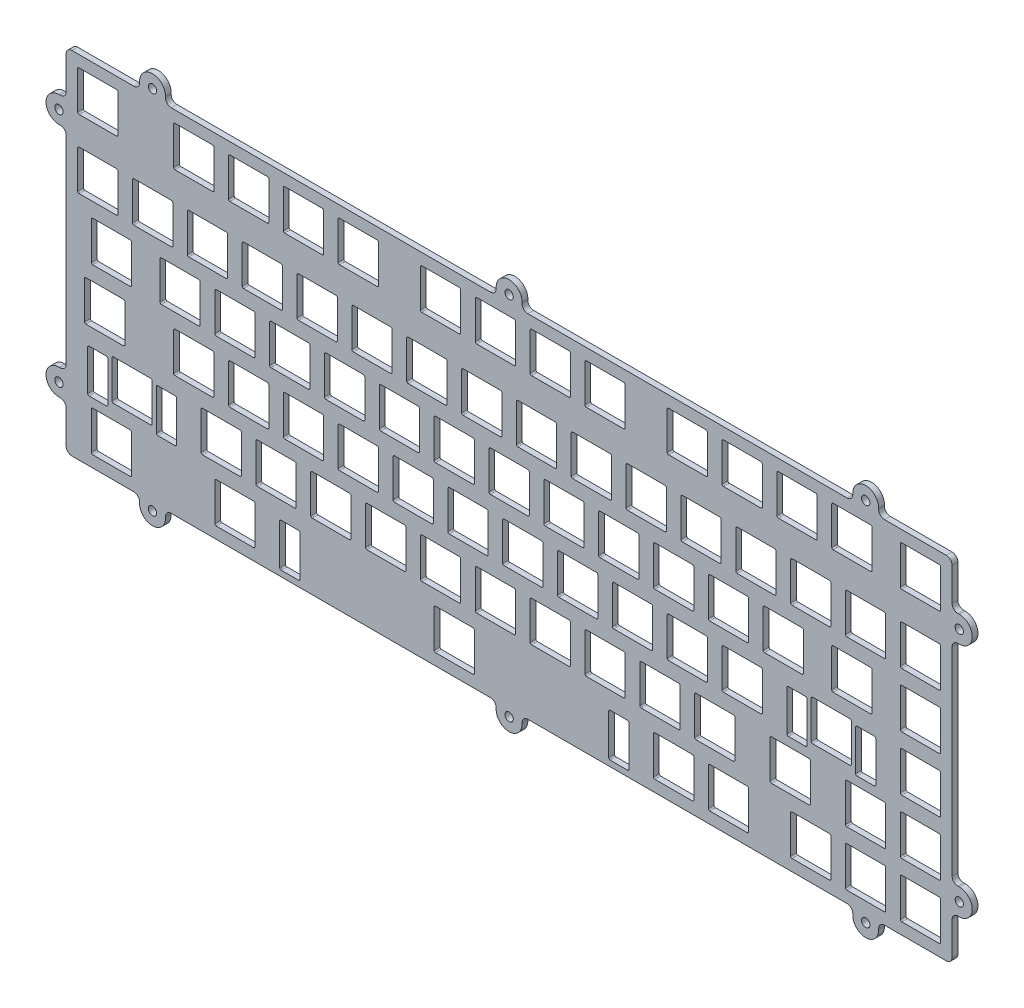
SolidWorks part; units mm, degrees
material "Brass"
ref_plane "Front Plane" through (0, 0, 0) normal (0, 0, 1) x (1, 0, 0)
ref_plane "Top Plane" through (0, 0, 0) normal (0, 1, 0) x (1, 0, 0)
ref_plane "Right Plane" through (0, 0, 0) normal (1, 0, 0) x (0, 0, -1)
sketch "Base_Import_Plate" plane through (0, 0, 0) normal (0, 0, 1) x (1, 0, 0)
  line L0 (12.05, 126.0625) -> (26.05, 126.0625)
  line L1 (12.05, 112.0625) -> (26.05, 112.0625)
  line L2 (12.05, 126.0625) -> (12.05, 112.0625)
  line L3 (26.05, 126.0625) -> (26.05, 112.0625)
  line L4 (45.3875, 126.0625) -> (59.3875, 126.0625)
  line L5 (45.3875, 112.0625) -> (59.3875, 112.0625)
  line L6 (45.3875, 126.0625) -> (45.3875, 112.0625)
  line L7 (59.3875, 126.0625) -> (59.3875, 112.0625)
  line L8 (64.4375, 126.0625) -> (78.4375, 126.0625)
  line L9 (64.4375, 112.0625) -> (78.4375, 112.0625)
  line L10 (64.4375, 126.0625) -> (64.4375, 112.0625)
  line L11 (78.4375, 126.0625) -> (78.4375, 112.0625)
  line L12 (83.4875, 126.0625) -> (97.4875, 126.0625)
  line L13 (83.4875, 112.0625) -> (97.4875, 112.0625)
  line L14 (83.4875, 126.0625) -> (83.4875, 112.0625)
  line L15 (97.4875, 126.0625) -> (97.4875, 112.0625)
  line L16 (102.5375, 126.0625) -> (116.5375, 126.0625)
  line L17 (102.5375, 112.0625) -> (116.5375, 112.0625)
  line L18 (102.5375, 126.0625) -> (102.5375, 112.0625)
  line L19 (116.5375, 126.0625) -> (116.5375, 112.0625)
  line L20 (131.1125, 126.0625) -> (145.1125, 126.0625)
  line L21 (131.1125, 112.0625) -> (145.1125, 112.0625)
  line L22 (131.1125, 126.0625) -> (131.1125, 112.0625)
  line L23 (145.1125, 126.0625) -> (145.1125, 112.0625)
  line L24 (150.1625, 126.0625) -> (164.1625, 126.0625)
  line L25 (150.1625, 112.0625) -> (164.1625, 112.0625)
  line L26 (150.1625, 126.0625) -> (150.1625, 112.0625)
  line L27 (164.1625, 126.0625) -> (164.1625, 112.0625)
  line L28 (169.2125, 126.0625) -> (183.2125, 126.0625)
  line L29 (169.2125, 112.0625) -> (183.2125, 112.0625)
  line L30 (169.2125, 126.0625) -> (169.2125, 112.0625)
  line L31 (183.2125, 126.0625) -> (183.2125, 112.0625)
  line L32 (188.2625, 126.0625) -> (202.2625, 126.0625)
  line L33 (188.2625, 112.0625) -> (202.2625, 112.0625)
  line L34 (188.2625, 126.0625) -> (188.2625, 112.0625)
  line L35 (202.2625, 126.0625) -> (202.2625, 112.0625)
  line L36 (216.8375, 126.0625) -> (230.8375, 126.0625)
  line L37 (216.8375, 112.0625) -> (230.8375, 112.0625)
  line L38 (216.8375, 126.0625) -> (216.8375, 112.0625)
  line L39 (230.8375, 126.0625) -> (230.8375, 112.0625)
  line L40 (235.8875, 126.0625) -> (249.8875, 126.0625)
  line L41 (235.8875, 112.0625) -> (249.8875, 112.0625)
  line L42 (235.8875, 126.0625) -> (235.8875, 112.0625)
  line L43 (249.8875, 126.0625) -> (249.8875, 112.0625)
  line L44 (254.9375, 126.0625) -> (268.9375, 126.0625)
  line L45 (254.9375, 112.0625) -> (268.9375, 112.0625)
  line L46 (254.9375, 126.0625) -> (254.9375, 112.0625)
  line L47 (268.9375, 126.0625) -> (268.9375, 112.0625)
  line L48 (273.9875, 126.0625) -> (287.9875, 126.0625)
  line L49 (273.9875, 112.0625) -> (287.9875, 112.0625)
  line L50 (273.9875, 126.0625) -> (273.9875, 112.0625)
  line L51 (287.9875, 126.0625) -> (287.9875, 112.0625)
  line L52 (297.8, 126.0625) -> (311.8, 126.0625)
  line L53 (297.8, 112.0625) -> (311.8, 112.0625)
  line L54 (297.8, 126.0625) -> (297.8, 112.0625)
  line L55 (311.8, 126.0625) -> (311.8, 112.0625)
  line L56 (12.05, 102.25) -> (26.05, 102.25)
  line L57 (12.05, 88.25) -> (26.05, 88.25)
  line L58 (12.05, 102.25) -> (12.05, 88.25)
  line L59 (26.05, 102.25) -> (26.05, 88.25)
  line L60 (31.1, 102.25) -> (45.1, 102.25)
  line L61 (31.1, 88.25) -> (45.1, 88.25)
  line L62 (31.1, 102.25) -> (31.1, 88.25)
  line L63 (45.1, 102.25) -> (45.1, 88.25)
  line L64 (50.15, 102.25) -> (64.15, 102.25)
  line L65 (50.15, 88.25) -> (64.15, 88.25)
  line L66 (50.15, 102.25) -> (50.15, 88.25)
  line L67 (64.15, 102.25) -> (64.15, 88.25)
  line L68 (69.2, 102.25) -> (83.2, 102.25)
  line L69 (69.2, 88.25) -> (83.2, 88.25)
  line L70 (69.2, 102.25) -> (69.2, 88.25)
  line L71 (83.2, 102.25) -> (83.2, 88.25)
  line L72 (88.25, 102.25) -> (102.25, 102.25)
  line L73 (88.25, 88.25) -> (102.25, 88.25)
  line L74 (88.25, 102.25) -> (88.25, 88.25)
  line L75 (102.25, 102.25) -> (102.25, 88.25)
  line L76 (107.3, 102.25) -> (121.3, 102.25)
  line L77 (107.3, 88.25) -> (121.3, 88.25)
  line L78 (107.3, 102.25) -> (107.3, 88.25)
  line L79 (121.3, 102.25) -> (121.3, 88.25)
  line L80 (126.35, 102.25) -> (140.35, 102.25)
  line L81 (126.35, 88.25) -> (140.35, 88.25)
  line L82 (126.35, 102.25) -> (126.35, 88.25)
  line L83 (140.35, 102.25) -> (140.35, 88.25)
  line L84 (145.4, 102.25) -> (159.4, 102.25)
  line L85 (145.4, 88.25) -> (159.4, 88.25)
  line L86 (145.4, 102.25) -> (145.4, 88.25)
  line L87 (159.4, 102.25) -> (159.4, 88.25)
  line L88 (164.45, 102.25) -> (178.45, 102.25)
  line L89 (164.45, 88.25) -> (178.45, 88.25)
  line L90 (164.45, 102.25) -> (164.45, 88.25)
  line L91 (178.45, 102.25) -> (178.45, 88.25)
  line L92 (183.5, 102.25) -> (197.5, 102.25)
  line L93 (183.5, 88.25) -> (197.5, 88.25)
  line L94 (183.5, 102.25) -> (183.5, 88.25)
  line L95 (197.5, 102.25) -> (197.5, 88.25)
  line L96 (202.55, 102.25) -> (216.55, 102.25)
  line L97 (202.55, 88.25) -> (216.55, 88.25)
  line L98 (202.55, 102.25) -> (202.55, 88.25)
  line L99 (216.55, 102.25) -> (216.55, 88.25)
  line L100 (221.6, 102.25) -> (235.6, 102.25)
  line L101 (221.6, 88.25) -> (235.6, 88.25)
  line L102 (221.6, 102.25) -> (221.6, 88.25)
  line L103 (235.6, 102.25) -> (235.6, 88.25)
  line L104 (240.65, 102.25) -> (254.65, 102.25)
  line L105 (240.65, 88.25) -> (254.65, 88.25)
  line L106 (240.65, 102.25) -> (240.65, 88.25)
  line L107 (254.65, 102.25) -> (254.65, 88.25)
  line L108 (259.7, 102.25) -> (273.7, 102.25)
  line L109 (259.7, 88.25) -> (273.7, 88.25)
  line L110 (259.7, 102.25) -> (259.7, 88.25)
  line L111 (273.7, 102.25) -> (273.7, 88.25)
  line L112 (278.75, 102.25) -> (292.75, 102.25)
  line L113 (278.75, 88.25) -> (292.75, 88.25)
  line L114 (278.75, 102.25) -> (278.75, 88.25)
  line L115 (292.75, 102.25) -> (292.75, 88.25)
  line L116 (297.8, 102.25) -> (311.8, 102.25)
  line L117 (297.8, 88.25) -> (311.8, 88.25)
  line L118 (297.8, 102.25) -> (297.8, 88.25)
  line L119 (311.8, 102.25) -> (311.8, 88.25)
  line L120 (16.8125, 83.2) -> (30.8125, 83.2)
  line L121 (16.8125, 69.2) -> (30.8125, 69.2)
  line L122 (16.8125, 83.2) -> (16.8125, 69.2)
  line L123 (30.8125, 83.2) -> (30.8125, 69.2)
  line L124 (40.625, 83.2) -> (54.625, 83.2)
  line L125 (40.625, 69.2) -> (54.625, 69.2)
  line L126 (40.625, 83.2) -> (40.625, 69.2)
  line L127 (54.625, 83.2) -> (54.625, 69.2)
  line L128 (59.675, 83.2) -> (73.675, 83.2)
  line L129 (59.675, 69.2) -> (73.675, 69.2)
  line L130 (59.675, 83.2) -> (59.675, 69.2)
  line L131 (73.675, 83.2) -> (73.675, 69.2)
  line L132 (78.725, 83.2) -> (92.725, 83.2)
  line L133 (78.725, 69.2) -> (92.725, 69.2)
  line L134 (78.725, 83.2) -> (78.725, 69.2)
  line L135 (92.725, 83.2) -> (92.725, 69.2)
  line L136 (97.775, 83.2) -> (111.775, 83.2)
  line L137 (97.775, 69.2) -> (111.775, 69.2)
  line L138 (97.775, 83.2) -> (97.775, 69.2)
  line L139 (111.775, 83.2) -> (111.775, 69.2)
  line L140 (116.825, 83.2) -> (130.825, 83.2)
  line L141 (116.825, 69.2) -> (130.825, 69.2)
  line L142 (116.825, 83.2) -> (116.825, 69.2)
  line L143 (130.825, 83.2) -> (130.825, 69.2)
  line L144 (135.875, 83.2) -> (149.875, 83.2)
  line L145 (135.875, 69.2) -> (149.875, 69.2)
  line L146 (135.875, 83.2) -> (135.875, 69.2)
  line L147 (149.875, 83.2) -> (149.875, 69.2)
  line L148 (154.925, 83.2) -> (168.925, 83.2)
  line L149 (154.925, 69.2) -> (168.925, 69.2)
  line L150 (154.925, 83.2) -> (154.925, 69.2)
  line L151 (168.925, 83.2) -> (168.925, 69.2)
  line L152 (173.975, 83.2) -> (187.975, 83.2)
  line L153 (173.975, 69.2) -> (187.975, 69.2)
  line L154 (173.975, 83.2) -> (173.975, 69.2)
  line L155 (187.975, 83.2) -> (187.975, 69.2)
  line L156 (193.025, 83.2) -> (207.025, 83.2)
  line L157 (193.025, 69.2) -> (207.025, 69.2)
  line L158 (193.025, 83.2) -> (193.025, 69.2)
  line L159 (207.025, 83.2) -> (207.025, 69.2)
  line L160 (212.075, 83.2) -> (226.075, 83.2)
  line L161 (212.075, 69.2) -> (226.075, 69.2)
  line L162 (212.075, 83.2) -> (212.075, 69.2)
  line L163 (226.075, 83.2) -> (226.075, 69.2)
  line L164 (231.125, 83.2) -> (245.125, 83.2)
  line L165 (231.125, 69.2) -> (245.125, 69.2)
  line L166 (231.125, 83.2) -> (231.125, 69.2)
  line L167 (245.125, 83.2) -> (245.125, 69.2)
  line L168 (250.175, 83.2) -> (264.175, 83.2)
  line L169 (250.175, 69.2) -> (264.175, 69.2)
  line L170 (250.175, 83.2) -> (250.175, 69.2)
  line L171 (264.175, 83.2) -> (264.175, 69.2)
  line L172 (273.9875, 83.2) -> (287.9875, 83.2)
  line L173 (273.9875, 69.2) -> (287.9875, 69.2)
  line L174 (273.9875, 83.2) -> (273.9875, 69.2)
  line L175 (287.9875, 83.2) -> (287.9875, 69.2)
  line L176 (297.8, 83.2) -> (311.8, 83.2)
  line L177 (297.8, 69.2) -> (311.8, 69.2)
  line L178 (297.8, 83.2) -> (297.8, 69.2)
  line L179 (311.8, 83.2) -> (311.8, 69.2)
  line L180 (14.4312, 64.15) -> (28.4312, 64.15)
  line L181 (14.4312, 50.15) -> (28.4312, 50.15)
  line L182 (14.4312, 64.15) -> (14.4312, 50.15)
  line L183 (28.4312, 64.15) -> (28.4312, 50.15)
  line L184 (45.3875, 64.15) -> (59.3875, 64.15)
  line L185 (45.3875, 50.15) -> (59.3875, 50.15)
  line L186 (45.3875, 64.15) -> (45.3875, 50.15)
  line L187 (59.3875, 64.15) -> (59.3875, 50.15)
  line L188 (64.4375, 64.15) -> (78.4375, 64.15)
  line L189 (64.4375, 50.15) -> (78.4375, 50.15)
  line L190 (64.4375, 64.15) -> (64.4375, 50.15)
  line L191 (78.4375, 64.15) -> (78.4375, 50.15)
  line L192 (83.4875, 64.15) -> (97.4875, 64.15)
  line L193 (83.4875, 50.15) -> (97.4875, 50.15)
  line L194 (83.4875, 64.15) -> (83.4875, 50.15)
  line L195 (97.4875, 64.15) -> (97.4875, 50.15)
  line L196 (102.5375, 64.15) -> (116.5375, 64.15)
  line L197 (102.5375, 50.15) -> (116.5375, 50.15)
  line L198 (102.5375, 64.15) -> (102.5375, 50.15)
  line L199 (116.5375, 64.15) -> (116.5375, 50.15)
  line L200 (121.5875, 64.15) -> (135.5875, 64.15)
  line L201 (121.5875, 50.15) -> (135.5875, 50.15)
  line L202 (121.5875, 64.15) -> (121.5875, 50.15)
  line L203 (135.5875, 64.15) -> (135.5875, 50.15)
  line L204 (140.6375, 64.15) -> (154.6375, 64.15)
  line L205 (140.6375, 50.15) -> (154.6375, 50.15)
  line L206 (140.6375, 64.15) -> (140.6375, 50.15)
  line L207 (154.6375, 64.15) -> (154.6375, 50.15)
  line L208 (159.6875, 64.15) -> (173.6875, 64.15)
  line L209 (159.6875, 50.15) -> (173.6875, 50.15)
  line L210 (159.6875, 64.15) -> (159.6875, 50.15)
  line L211 (173.6875, 64.15) -> (173.6875, 50.15)
  line L212 (178.7375, 64.15) -> (192.7375, 64.15)
  line L213 (178.7375, 50.15) -> (192.7375, 50.15)
  line L214 (178.7375, 64.15) -> (178.7375, 50.15)
  line L215 (192.7375, 64.15) -> (192.7375, 50.15)
  line L216 (197.7875, 64.15) -> (211.7875, 64.15)
  line L217 (197.7875, 50.15) -> (211.7875, 50.15)
  line L218 (197.7875, 64.15) -> (197.7875, 50.15)
  line L219 (211.7875, 64.15) -> (211.7875, 50.15)
  line L220 (216.8375, 64.15) -> (230.8375, 64.15)
  line L221 (216.8375, 50.15) -> (230.8375, 50.15)
  line L222 (216.8375, 64.15) -> (216.8375, 50.15)
  line L223 (230.8375, 64.15) -> (230.8375, 50.15)
  line L224 (235.8875, 64.15) -> (249.8875, 64.15)
  line L225 (235.8875, 50.15) -> (249.8875, 50.15)
  line L226 (235.8875, 64.15) -> (235.8875, 50.15)
  line L227 (249.8875, 64.15) -> (249.8875, 50.15)
  line L228 (266.8437, 64.15) -> (280.8437, 64.15)
  line L229 (266.8437, 50.15) -> (280.8437, 50.15)
  line L230 (266.8437, 64.15) -> (266.8437, 50.15)
  line L231 (280.8437, 64.15) -> (280.8437, 50.15)
  line L232 (282.2817, 63.15) -> (289.2817, 63.15)
  line L233 (282.2817, 48.15) -> (289.2817, 48.15)
  line L234 (282.2817, 63.15) -> (282.2817, 48.15)
  line L235 (289.2817, 63.15) -> (289.2817, 48.15)
  line L236 (258.4057, 63.15) -> (265.4057, 63.15)
  line L237 (258.4057, 48.15) -> (265.4057, 48.15)
  line L238 (258.4057, 63.15) -> (258.4057, 48.15)
  line L239 (265.4057, 63.15) -> (265.4057, 48.15)
  line L240 (297.8, 64.15) -> (311.8, 64.15)
  line L241 (297.8, 50.15) -> (311.8, 50.15)
  line L242 (297.8, 64.15) -> (297.8, 50.15)
  line L243 (311.8, 64.15) -> (311.8, 50.15)
  line L244 (23.9562, 45.1) -> (37.9562, 45.1)
  line L245 (23.9562, 31.1) -> (37.9562, 31.1)
  line L246 (23.9562, 45.1) -> (23.9562, 31.1)
  line L247 (37.9562, 45.1) -> (37.9562, 31.1)
  line L248 (39.3942, 44.1) -> (46.3942, 44.1)
  line L249 (39.3942, 29.1) -> (46.3942, 29.1)
  line L250 (39.3942, 44.1) -> (39.3942, 29.1)
  line L251 (46.3942, 44.1) -> (46.3942, 29.1)
  line L252 (15.5182, 44.1) -> (22.5182, 44.1)
  line L253 (15.5182, 29.1) -> (22.5182, 29.1)
  line L254 (15.5182, 44.1) -> (15.5182, 29.1)
  line L255 (22.5182, 44.1) -> (22.5182, 29.1)
  line L256 (54.9125, 45.1) -> (68.9125, 45.1)
  line L257 (54.9125, 31.1) -> (68.9125, 31.1)
  line L258 (54.9125, 45.1) -> (54.9125, 31.1)
  line L259 (68.9125, 45.1) -> (68.9125, 31.1)
  line L260 (73.9625, 45.1) -> (87.9625, 45.1)
  line L261 (73.9625, 31.1) -> (87.9625, 31.1)
  line L262 (73.9625, 45.1) -> (73.9625, 31.1)
  line L263 (87.9625, 45.1) -> (87.9625, 31.1)
  line L264 (93.0125, 45.1) -> (107.0125, 45.1)
  line L265 (93.0125, 31.1) -> (107.0125, 31.1)
  line L266 (93.0125, 45.1) -> (93.0125, 31.1)
  line L267 (107.0125, 45.1) -> (107.0125, 31.1)
  line L268 (112.0625, 45.1) -> (126.0625, 45.1)
  line L269 (112.0625, 31.1) -> (126.0625, 31.1)
  line L270 (112.0625, 45.1) -> (112.0625, 31.1)
  line L271 (126.0625, 45.1) -> (126.0625, 31.1)
  line L272 (131.1125, 45.1) -> (145.1125, 45.1)
  line L273 (131.1125, 31.1) -> (145.1125, 31.1)
  line L274 (131.1125, 45.1) -> (131.1125, 31.1)
  line L275 (145.1125, 45.1) -> (145.1125, 31.1)
  line L276 (150.1625, 45.1) -> (164.1625, 45.1)
  line L277 (150.1625, 31.1) -> (164.1625, 31.1)
  line L278 (150.1625, 45.1) -> (150.1625, 31.1)
  line L279 (164.1625, 45.1) -> (164.1625, 31.1)
  line L280 (169.2125, 45.1) -> (183.2125, 45.1)
  line L281 (169.2125, 31.1) -> (183.2125, 31.1)
  line L282 (169.2125, 45.1) -> (169.2125, 31.1)
  line L283 (183.2125, 45.1) -> (183.2125, 31.1)
  line L284 (188.2625, 45.1) -> (202.2625, 45.1)
  line L285 (188.2625, 31.1) -> (202.2625, 31.1)
  line L286 (188.2625, 45.1) -> (188.2625, 31.1)
  line L287 (202.2625, 45.1) -> (202.2625, 31.1)
  line L288 (207.3125, 45.1) -> (221.3125, 45.1)
  line L289 (207.3125, 31.1) -> (221.3125, 31.1)
  line L290 (207.3125, 45.1) -> (207.3125, 31.1)
  line L291 (221.3125, 45.1) -> (221.3125, 31.1)
  line L292 (226.3625, 45.1) -> (240.3625, 45.1)
  line L293 (226.3625, 31.1) -> (240.3625, 31.1)
  line L294 (226.3625, 45.1) -> (226.3625, 31.1)
  line L295 (240.3625, 45.1) -> (240.3625, 31.1)
  line L296 (252.5562, 45.1) -> (266.5562, 45.1)
  line L297 (252.5562, 31.1) -> (266.5562, 31.1)
  line L298 (252.5562, 45.1) -> (252.5562, 31.1)
  line L299 (266.5562, 45.1) -> (266.5562, 31.1)
  line L300 (278.75, 45.1) -> (292.75, 45.1)
  line L301 (278.75, 31.1) -> (292.75, 31.1)
  line L302 (278.75, 45.1) -> (278.75, 31.1)
  line L303 (292.75, 45.1) -> (292.75, 31.1)
  line L304 (297.8, 45.1) -> (311.8, 45.1)
  line L305 (297.8, 31.1) -> (311.8, 31.1)
  line L306 (297.8, 45.1) -> (297.8, 31.1)
  line L307 (311.8, 45.1) -> (311.8, 31.1)
  line L308 (16.8125, 26.05) -> (30.8125, 26.05)
  line L309 (16.8125, 12.05) -> (30.8125, 12.05)
  line L310 (16.8125, 26.05) -> (16.8125, 12.05)
  line L311 (30.8125, 26.05) -> (30.8125, 12.05)
  line L312 (59.675, 26.05) -> (73.675, 26.05)
  line L313 (59.675, 12.05) -> (73.675, 12.05)
  line L314 (59.675, 26.05) -> (59.675, 12.05)
  line L315 (73.675, 26.05) -> (73.675, 12.05)
  line L316 (135.875, 26.05) -> (149.875, 26.05)
  line L317 (135.875, 12.05) -> (149.875, 12.05)
  line L318 (135.875, 26.05) -> (135.875, 12.05)
  line L319 (149.875, 26.05) -> (149.875, 12.05)
  line L320 (196.525, 25.05) -> (203.525, 25.05)
  line L321 (196.525, 10.05) -> (203.525, 10.05)
  line L322 (196.525, 25.05) -> (196.525, 10.05)
  line L323 (203.525, 25.05) -> (203.525, 10.05)
  line L324 (82.225, 25.05) -> (89.225, 25.05)
  line L325 (82.225, 10.05) -> (89.225, 10.05)
  line L326 (82.225, 25.05) -> (82.225, 10.05)
  line L327 (89.225, 25.05) -> (89.225, 10.05)
  line L328 (212.075, 26.05) -> (226.075, 26.05)
  line L329 (212.075, 12.05) -> (226.075, 12.05)
  line L330 (212.075, 26.05) -> (212.075, 12.05)
  line L331 (226.075, 26.05) -> (226.075, 12.05)
  line L332 (231.125, 26.05) -> (245.125, 26.05)
  line L333 (231.125, 12.05) -> (245.125, 12.05)
  line L334 (231.125, 26.05) -> (231.125, 12.05)
  line L335 (245.125, 26.05) -> (245.125, 12.05)
  line L336 (259.7, 26.05) -> (273.7, 26.05)
  line L337 (259.7, 12.05) -> (273.7, 12.05)
  line L338 (259.7, 26.05) -> (259.7, 12.05)
  line L339 (273.7, 26.05) -> (273.7, 12.05)
  line L340 (278.75, 26.05) -> (292.75, 26.05)
  line L341 (278.75, 12.05) -> (292.75, 12.05)
  line L342 (278.75, 26.05) -> (278.75, 12.05)
  line L343 (292.75, 26.05) -> (292.75, 12.05)
  line L344 (297.8, 26.05) -> (311.8, 26.05)
  line L345 (297.8, 12.05) -> (311.8, 12.05)
  line L346 (297.8, 26.05) -> (297.8, 12.05)
  line L347 (311.8, 26.05) -> (311.8, 12.05)
  circle A0 centre (19.05, 119.0625) radius 2
  circle A1 centre (19.05, 95.25) radius 2
  circle A2 centre (38.1, 95.25) radius 2
  circle A3 centre (52.3875, 119.0625) radius 2
  circle A4 centre (71.4375, 119.0625) radius 2
  circle A5 centre (90.4875, 119.0625) radius 2
  circle A6 centre (109.5375, 119.0625) radius 2
  circle A7 centre (138.1125, 119.0625) radius 2
  circle A8 centre (157.1625, 119.0625) radius 2
  circle A9 centre (176.2125, 119.0625) radius 2
  circle A10 centre (195.2625, 119.0625) radius 2
  circle A11 centre (223.8375, 119.0625) radius 2
  circle A12 centre (242.8875, 119.0625) radius 2
  circle A13 centre (261.9375, 119.0625) radius 2
  circle A14 centre (280.9875, 119.0625) radius 2
  circle A15 centre (304.8, 119.0625) radius 2
  circle A16 centre (57.15, 95.25) radius 2
  circle A17 centre (76.2, 95.25) radius 2
  circle A18 centre (95.25, 95.25) radius 2
  circle A19 centre (114.3, 95.25) radius 2
  circle A20 centre (133.35, 95.25) radius 2
  circle A21 centre (152.4, 95.25) radius 2
  circle A22 centre (171.45, 95.25) radius 2
  circle A23 centre (190.5, 95.25) radius 2
  circle A24 centre (209.55, 95.25) radius 2
  circle A25 centre (228.6, 95.25) radius 2
  circle A26 centre (247.65, 95.25) radius 2
  circle A27 centre (266.7, 95.25) radius 2
  circle A28 centre (285.75, 95.25) radius 2
  circle A29 centre (304.8, 95.25) radius 2
  circle A30 centre (304.8, 76.2) radius 2
  circle A31 centre (304.8, 57.15) radius 2
  circle A32 centre (304.8, 38.1) radius 2
  circle A33 centre (304.8, 19.05) radius 2
  circle A34 centre (285.75, 19.05) radius 2
  circle A35 centre (285.75, 38.1) radius 2
  circle A36 centre (273.8438, 57.15) radius 2
  circle A37 centre (280.9875, 76.2) radius 2
  circle A38 centre (257.175, 76.2) radius 2
  circle A39 centre (238.125, 76.2) radius 2
  circle A40 centre (219.075, 76.2) radius 2
  circle A41 centre (200.025, 76.2) radius 2
  circle A42 centre (180.975, 76.2) radius 2
  circle A43 centre (161.925, 76.2) radius 2
  circle A44 centre (142.875, 76.2) radius 2
  circle A45 centre (123.825, 76.2) radius 2
  circle A46 centre (104.775, 76.2) radius 2
  circle A47 centre (85.725, 76.2) radius 2
  circle A48 centre (66.675, 76.2) radius 2
  circle A49 centre (47.625, 76.2) radius 2
  circle A50 centre (23.8125, 76.2) radius 2
  circle A51 centre (21.4312, 57.15) radius 2
  circle A52 centre (30.9562, 38.1) radius 2
  circle A53 centre (52.3875, 57.15) radius 2
  circle A54 centre (71.4375, 57.15) radius 2
  circle A55 centre (90.4875, 57.15) radius 2
  circle A56 centre (61.9125, 38.1) radius 2
  circle A57 centre (66.675, 19.05) radius 2
  circle A58 centre (23.8125, 19.05) radius 2
  circle A59 centre (142.875, 19.05) radius 2
  circle A60 centre (80.9625, 38.1) radius 2
  circle A61 centre (100.0125, 38.1) radius 2
  circle A62 centre (119.0625, 38.1) radius 2
  circle A63 centre (109.5375, 57.15) radius 2
  circle A64 centre (128.5875, 57.15) radius 2
  circle A65 centre (147.6375, 57.15) radius 2
  circle A66 centre (138.1125, 38.1) radius 2
  circle A67 centre (157.1625, 38.1) radius 2
  circle A68 centre (166.6875, 57.15) radius 2
  circle A69 centre (185.7375, 57.15) radius 2
  circle A70 centre (204.7875, 57.15) radius 2
  circle A71 centre (223.8375, 57.15) radius 2
  circle A72 centre (242.8875, 57.15) radius 2
  circle A73 centre (259.5563, 38.1) radius 2
  circle A74 centre (266.7, 19.05) radius 2
  circle A75 centre (238.125, 19.05) radius 2
  circle A76 centre (219.075, 19.05) radius 2
  circle A77 centre (214.3125, 38.1) radius 2
  circle A78 centre (233.3625, 38.1) radius 2
  circle A79 centre (195.2625, 38.1) radius 2
  circle A80 centre (176.2125, 38.1) radius 2
  dimension "D1" = 19.05
  dimension "D2" = 95.25
sketch "Plate v1" plane through (0, 0, 0) normal (0, 0, 1) x (1, 0, 0)
  line L0 (187.975, 83.2) -> (187.975, 69.2) construction
  line L2 (311.8, 26.05) -> (311.8, 12.05) construction
  line L3 (297.8, 12.05) -> (311.8, 12.05) construction
  line L4 (297.8, 26.05) -> (297.8, 12.05) construction
  line L5 (297.8, 26.05) -> (311.8, 26.05) construction
  line L6 (311.8, 45.1) -> (311.8, 31.1) construction
  line L7 (297.8, 31.1) -> (311.8, 31.1) construction
  line L8 (297.8, 45.1) -> (297.8, 31.1) construction
  line L9 (297.8, 45.1) -> (311.8, 45.1) construction
  line L10 (311.8, 64.15) -> (311.8, 50.15) construction
  line L11 (297.8, 50.15) -> (311.8, 50.15) construction
  line L12 (297.8, 64.15) -> (297.8, 50.15) construction
  line L13 (297.8, 64.15) -> (311.8, 64.15) construction
  line L14 (297.8, 69.2) -> (311.8, 69.2) construction
  line L15 (297.8, 83.2) -> (297.8, 69.2) construction
  line L16 (297.8, 83.2) -> (311.8, 83.2) construction
  line L17 (297.8, 88.25) -> (311.8, 88.25) construction
  line L18 (311.8, 102.25) -> (311.8, 88.25) construction
  line L19 (297.8, 102.25) -> (311.8, 102.25) construction
  line L20 (297.8, 102.25) -> (297.8, 88.25) construction
  line L21 (297.8, 112.0625) -> (311.8, 112.0625) construction
  line L22 (311.8, 126.0625) -> (311.8, 112.0625) construction
  line L23 (297.8, 126.0625) -> (311.8, 126.0625) construction
  line L24 (297.8, 126.0625) -> (297.8, 112.0625) construction
  line L25 (287.9875, 126.0625) -> (287.9875, 112.0625) construction
  line L26 (273.9875, 126.0625) -> (287.9875, 126.0625) construction
  line L27 (273.9875, 126.0625) -> (273.9875, 112.0625) construction
  line L28 (273.9875, 112.0625) -> (287.9875, 112.0625) construction
  line L29 (278.75, 102.25) -> (292.75, 102.25) construction
  line L30 (292.75, 102.25) -> (292.75, 88.25) construction
  line L31 (278.75, 88.25) -> (292.75, 88.25) construction
  line L32 (278.75, 102.25) -> (278.75, 88.25) construction
  line L33 (259.7, 102.25) -> (273.7, 102.25) construction
  line L34 (273.7, 102.25) -> (273.7, 88.25) construction
  line L35 (259.7, 102.25) -> (259.7, 88.25) construction
  line L36 (259.7, 88.25) -> (273.7, 88.25) construction
  line L37 (273.9875, 83.2) -> (287.9875, 83.2) construction
  line L38 (287.9875, 83.2) -> (287.9875, 69.2) construction
  line L39 (273.9875, 69.2) -> (287.9875, 69.2) construction
  line L40 (273.9875, 83.2) -> (273.9875, 69.2) construction
  line L41 (282.2817, 63.15) -> (289.2817, 63.15) construction
  line L42 (289.2817, 63.15) -> (289.2817, 48.15) construction
  line L43 (282.2817, 48.15) -> (289.2817, 48.15) construction
  line L44 (282.2817, 63.15) -> (282.2817, 48.15) construction
  line L45 (280.8437, 64.15) -> (280.8437, 50.15) construction
  line L46 (266.8437, 64.15) -> (280.8437, 64.15) construction
  line L47 (266.8437, 50.15) -> (280.8437, 50.15) construction
  line L48 (266.8437, 64.15) -> (266.8437, 50.15) construction
  line L49 (265.4057, 63.15) -> (265.4057, 48.15) construction
  line L50 (258.4057, 63.15) -> (265.4057, 63.15) construction
  line L51 (258.4057, 63.15) -> (258.4057, 48.15) construction
  line L52 (258.4057, 48.15) -> (265.4057, 48.15) construction
  line L53 (252.5562, 45.1) -> (266.5562, 45.1) construction
  line L54 (266.5562, 45.1) -> (266.5562, 31.1) construction
  line L55 (252.5562, 31.1) -> (266.5562, 31.1) construction
  line L56 (252.5562, 45.1) -> (252.5562, 31.1) construction
  line L57 (278.75, 45.1) -> (292.75, 45.1) construction
  line L58 (292.75, 45.1) -> (292.75, 31.1) construction
  line L59 (278.75, 31.1) -> (292.75, 31.1) construction
  line L60 (278.75, 45.1) -> (278.75, 31.1) construction
  line L61 (292.75, 26.05) -> (292.75, 12.05) construction
  line L62 (278.75, 26.05) -> (292.75, 26.05) construction
  line L63 (278.75, 12.05) -> (292.75, 12.05) construction
  line L64 (278.75, 26.05) -> (278.75, 12.05) construction
  line L65 (273.7, 26.05) -> (273.7, 12.05) construction
  line L66 (259.7, 26.05) -> (273.7, 26.05) construction
  line L67 (259.7, 26.05) -> (259.7, 12.05) construction
  line L68 (259.7, 12.05) -> (273.7, 12.05) construction
  line L69 (245.125, 26.05) -> (245.125, 12.05) construction
  line L70 (231.125, 26.05) -> (245.125, 26.05) construction
  line L71 (231.125, 26.05) -> (231.125, 12.05) construction
  line L72 (231.125, 12.05) -> (245.125, 12.05) construction
  line L73 (226.075, 26.05) -> (226.075, 12.05) construction
  line L74 (212.075, 12.05) -> (226.075, 12.05) construction
  line L75 (212.075, 26.05) -> (226.075, 26.05) construction
  line L76 (212.075, 26.05) -> (212.075, 12.05) construction
  line L77 (207.3125, 31.1) -> (221.3125, 31.1) construction
  line L78 (221.3125, 45.1) -> (221.3125, 31.1) construction
  line L79 (207.3125, 45.1) -> (221.3125, 45.1) construction
  line L80 (207.3125, 45.1) -> (207.3125, 31.1) construction
  line L81 (226.3625, 45.1) -> (226.3625, 31.1) construction
  line L82 (226.3625, 45.1) -> (240.3625, 45.1) construction
  line L83 (240.3625, 45.1) -> (240.3625, 31.1) construction
  line L84 (226.3625, 31.1) -> (240.3625, 31.1) construction
  line L85 (235.8875, 50.15) -> (249.8875, 50.15) construction
  line L86 (249.8875, 64.15) -> (249.8875, 50.15) construction
  line L87 (235.8875, 64.15) -> (249.8875, 64.15) construction
  line L88 (235.8875, 64.15) -> (235.8875, 50.15) construction
  line L89 (250.175, 83.2) -> (250.175, 69.2) construction
  line L90 (250.175, 83.2) -> (264.175, 83.2) construction
  line L91 (264.175, 83.2) -> (264.175, 69.2) construction
  line L92 (250.175, 69.2) -> (264.175, 69.2) construction
  line L93 (254.65, 102.25) -> (254.65, 88.25) construction
  line L94 (240.65, 102.25) -> (254.65, 102.25) construction
  line L95 (240.65, 102.25) -> (240.65, 88.25) construction
  line L96 (240.65, 88.25) -> (254.65, 88.25) construction
  line L97 (231.125, 83.2) -> (245.125, 83.2) construction
  line L98 (245.125, 83.2) -> (245.125, 69.2) construction
  line L99 (231.125, 69.2) -> (245.125, 69.2) construction
  line L100 (231.125, 83.2) -> (231.125, 69.2) construction
  line L101 (235.6, 102.25) -> (235.6, 88.25) construction
  line L102 (221.6, 88.25) -> (235.6, 88.25) construction
  line L103 (221.6, 102.25) -> (235.6, 102.25) construction
  line L104 (221.6, 102.25) -> (221.6, 88.25) construction
  line L105 (254.9375, 112.0625) -> (268.9375, 112.0625) construction
  line L106 (268.9375, 126.0625) -> (268.9375, 112.0625) construction
  line L107 (254.9375, 126.0625) -> (268.9375, 126.0625) construction
  line L108 (254.9375, 126.0625) -> (254.9375, 112.0625) construction
  line L109 (249.8875, 126.0625) -> (249.8875, 112.0625) construction
  line L110 (235.8875, 112.0625) -> (249.8875, 112.0625) construction
  line L111 (235.8875, 126.0625) -> (249.8875, 126.0625) construction
  line L112 (235.8875, 126.0625) -> (235.8875, 112.0625) construction
  line L113 (230.8375, 126.0625) -> (230.8375, 112.0625) construction
  line L114 (216.8375, 112.0625) -> (230.8375, 112.0625) construction
  line L115 (216.8375, 126.0625) -> (230.8375, 126.0625) construction
  line L116 (216.8375, 126.0625) -> (216.8375, 112.0625) construction
  line L117 (188.2625, 112.0625) -> (202.2625, 112.0625) construction
  line L118 (202.2625, 126.0625) -> (202.2625, 112.0625) construction
  line L119 (188.2625, 126.0625) -> (202.2625, 126.0625) construction
  line L120 (188.2625, 126.0625) -> (188.2625, 112.0625) construction
  line L121 (183.2125, 126.0625) -> (183.2125, 112.0625) construction
  line L122 (169.2125, 126.0625) -> (183.2125, 126.0625) construction
  line L123 (150.1625, 126.0625) -> (164.1625, 126.0625) construction
  line L124 (131.1125, 126.0625) -> (145.1125, 126.0625) construction
  line L125 (102.5375, 126.0625) -> (116.5375, 126.0625) construction
  line L126 (83.4875, 126.0625) -> (97.4875, 126.0625) construction
  line L127 (64.4375, 126.0625) -> (78.4375, 126.0625) construction
  line L128 (45.3875, 126.0625) -> (59.3875, 126.0625) construction
  line L129 (12.05, 126.0625) -> (26.05, 126.0625) construction
  line L130 (12.05, 126.0625) -> (12.05, 112.0625) construction
  line L131 (12.05, 112.0625) -> (26.05, 112.0625) construction
  line L132 (26.05, 126.0625) -> (26.05, 112.0625) construction
  line L133 (45.3875, 126.0625) -> (45.3875, 112.0625) construction
  line L134 (45.3875, 112.0625) -> (59.3875, 112.0625) construction
  line L135 (59.3875, 126.0625) -> (59.3875, 112.0625) construction
  line L136 (64.4375, 126.0625) -> (64.4375, 112.0625) construction
  line L137 (64.4375, 112.0625) -> (78.4375, 112.0625) construction
  line L138 (78.4375, 126.0625) -> (78.4375, 112.0625) construction
  line L139 (83.4875, 112.0625) -> (97.4875, 112.0625) construction
  line L140 (97.4875, 126.0625) -> (97.4875, 112.0625) construction
  line L141 (83.4875, 126.0625) -> (83.4875, 112.0625) construction
  line L142 (102.5375, 126.0625) -> (102.5375, 112.0625) construction
  line L143 (116.5375, 126.0625) -> (116.5375, 112.0625) construction
  line L144 (102.5375, 112.0625) -> (116.5375, 112.0625) construction
  line L145 (131.1125, 126.0625) -> (131.1125, 112.0625) construction
  line L146 (131.1125, 112.0625) -> (145.1125, 112.0625) construction
  line L147 (145.1125, 126.0625) -> (145.1125, 112.0625) construction
  line L148 (150.1625, 126.0625) -> (150.1625, 112.0625) construction
  line L149 (164.1625, 126.0625) -> (164.1625, 112.0625) construction
  line L150 (169.2125, 126.0625) -> (169.2125, 112.0625) construction
  line L151 (169.2125, 112.0625) -> (183.2125, 112.0625) construction
  line L152 (150.1625, 112.0625) -> (164.1625, 112.0625) construction
  line L153 (202.55, 102.25) -> (216.55, 102.25) construction
  line L154 (216.55, 102.25) -> (216.55, 88.25) construction
  line L155 (202.55, 88.25) -> (216.55, 88.25) construction
  line L156 (202.55, 102.25) -> (202.55, 88.25) construction
  line L157 (183.5, 102.25) -> (197.5, 102.25) construction
  line L158 (197.5, 102.25) -> (197.5, 88.25) construction
  line L159 (183.5, 88.25) -> (197.5, 88.25) construction
  line L160 (193.025, 83.2) -> (207.025, 83.2) construction
  line L161 (212.075, 83.2) -> (226.075, 83.2) construction
  line L162 (226.075, 83.2) -> (226.075, 69.2) construction
  line L163 (212.075, 69.2) -> (226.075, 69.2) construction
  line L164 (230.8375, 64.15) -> (230.8375, 50.15) construction
  line L165 (216.8375, 64.15) -> (230.8375, 64.15) construction
  line L166 (216.8375, 64.15) -> (216.8375, 50.15) construction
  line L167 (216.8375, 50.15) -> (230.8375, 50.15) construction
  line L168 (202.2625, 45.1) -> (202.2625, 31.1) construction
  line L169 (203.525, 25.05) -> (203.525, 10.05) construction
  line L170 (196.525, 25.05) -> (203.525, 25.05) construction
  line L171 (196.525, 25.05) -> (196.525, 10.05) construction
  line L172 (196.525, 10.05) -> (203.525, 10.05) construction
  line L173 (188.2625, 31.1) -> (202.2625, 31.1) construction
  line L174 (188.2625, 45.1) -> (188.2625, 31.1) construction
  line L175 (188.2625, 45.1) -> (202.2625, 45.1) construction
  line L176 (197.7875, 50.15) -> (211.7875, 50.15) construction
  line L177 (197.7875, 64.15) -> (211.7875, 64.15) construction
  line L178 (211.7875, 64.15) -> (211.7875, 50.15) construction
  line L179 (212.075, 83.2) -> (212.075, 69.2) construction
  line L180 (207.025, 83.2) -> (207.025, 69.2) construction
  line L181 (193.025, 69.2) -> (207.025, 69.2) construction
  line L182 (197.7875, 64.15) -> (197.7875, 50.15) construction
  line L183 (193.025, 83.2) -> (193.025, 69.2) construction
  line L184 (173.975, 83.2) -> (187.975, 83.2) construction
  line L185 (173.975, 69.2) -> (187.975, 69.2) construction
  line L186 (178.7375, 64.15) -> (192.7375, 64.15) construction
  line L187 (192.7375, 64.15) -> (192.7375, 50.15) construction
  line L188 (178.7375, 64.15) -> (178.7375, 50.15) construction
  line L189 (16.8125, 26.05) -> (16.8125, 12.05) construction
  line L190 (16.8125, 12.05) -> (30.8125, 12.05) construction
  line L191 (30.8125, 26.05) -> (30.8125, 12.05) construction
  line L192 (16.8125, 26.05) -> (30.8125, 26.05) construction
  line L193 (22.5182, 44.1) -> (22.5182, 29.1) construction
  line L194 (15.5182, 29.1) -> (22.5182, 29.1) construction
  line L195 (15.5182, 44.1) -> (15.5182, 29.1) construction
  line L196 (15.5182, 44.1) -> (22.5182, 44.1) construction
  line L197 (23.9562, 45.1) -> (23.9562, 31.1) construction
  line L198 (23.9562, 31.1) -> (37.9562, 31.1) construction
  line L199 (23.9562, 45.1) -> (37.9562, 45.1) construction
  line L200 (37.9562, 45.1) -> (37.9562, 31.1) construction
  line L201 (39.3942, 44.1) -> (39.3942, 29.1) construction
  line L202 (39.3942, 29.1) -> (46.3942, 29.1) construction
  line L203 (46.3942, 44.1) -> (46.3942, 29.1) construction
  line L204 (39.3942, 44.1) -> (46.3942, 44.1) construction
  line L205 (45.3875, 64.15) -> (45.3875, 50.15) construction
  line L206 (28.4312, 64.15) -> (28.4312, 50.15) construction
  line L207 (14.4312, 50.15) -> (28.4312, 50.15) construction
  line L208 (14.4312, 64.15) -> (14.4312, 50.15) construction
  line L209 (14.4312, 64.15) -> (28.4312, 64.15) construction
  line L210 (16.8125, 83.2) -> (16.8125, 69.2) construction
  line L211 (16.8125, 69.2) -> (30.8125, 69.2) construction
  line L212 (30.8125, 83.2) -> (30.8125, 69.2) construction
  line L213 (16.8125, 83.2) -> (30.8125, 83.2) construction
  line L214 (12.05, 102.25) -> (12.05, 88.25) construction
  line L215 (12.05, 88.25) -> (26.05, 88.25) construction
  line L216 (26.05, 102.25) -> (26.05, 88.25) construction
  line L217 (12.05, 102.25) -> (26.05, 102.25) construction
  line L218 (31.1, 102.25) -> (31.1, 88.25) construction
  line L219 (31.1, 88.25) -> (45.1, 88.25) construction
  line L220 (45.1, 102.25) -> (45.1, 88.25) construction
  line L221 (31.1, 102.25) -> (45.1, 102.25) construction
  line L222 (50.15, 102.25) -> (50.15, 88.25) construction
  line L223 (50.15, 102.25) -> (64.15, 102.25) construction
  line L224 (64.15, 102.25) -> (64.15, 88.25) construction
  line L225 (50.15, 88.25) -> (64.15, 88.25) construction
  line L226 (40.625, 83.2) -> (40.625, 69.2) construction
  line L227 (54.625, 83.2) -> (54.625, 69.2) construction
  line L228 (40.625, 83.2) -> (54.625, 83.2) construction
  line L229 (40.625, 69.2) -> (54.625, 69.2) construction
  line L230 (45.3875, 64.15) -> (59.3875, 64.15) construction
  line L231 (45.3875, 50.15) -> (59.3875, 50.15) construction
  line L232 (59.3875, 64.15) -> (59.3875, 50.15) construction
  line L233 (54.9125, 45.1) -> (54.9125, 31.1) construction
  line L234 (54.9125, 45.1) -> (68.9125, 45.1) construction
  line L235 (68.9125, 45.1) -> (68.9125, 31.1) construction
  line L236 (54.9125, 31.1) -> (68.9125, 31.1) construction
  line L237 (59.675, 12.05) -> (73.675, 12.05) construction
  line L238 (59.675, 26.05) -> (59.675, 12.05) construction
  line L239 (59.675, 26.05) -> (73.675, 26.05) construction
  line L240 (73.675, 26.05) -> (73.675, 12.05) construction
  line L241 (82.225, 25.05) -> (82.225, 10.05) construction
  line L242 (82.225, 10.05) -> (89.225, 10.05) construction
  line L243 (89.225, 25.05) -> (89.225, 10.05) construction
  line L244 (82.225, 25.05) -> (89.225, 25.05) construction
  line L245 (73.9625, 31.1) -> (87.9625, 31.1) construction
  line L246 (73.9625, 45.1) -> (73.9625, 31.1) construction
  line L247 (73.9625, 45.1) -> (87.9625, 45.1) construction
  line L248 (64.4375, 64.15) -> (64.4375, 50.15) construction
  line L249 (64.4375, 50.15) -> (78.4375, 50.15) construction
  line L250 (78.4375, 64.15) -> (78.4375, 50.15) construction
  line L251 (64.4375, 64.15) -> (78.4375, 64.15) construction
  line L252 (59.675, 83.2) -> (59.675, 69.2) construction
  line L253 (59.675, 69.2) -> (73.675, 69.2) construction
  line L254 (73.675, 83.2) -> (73.675, 69.2) construction
  line L255 (59.675, 83.2) -> (73.675, 83.2) construction
  line L256 (78.725, 83.2) -> (78.725, 69.2) construction
  line L257 (78.725, 69.2) -> (92.725, 69.2) construction
  line L258 (83.4875, 64.15) -> (83.4875, 50.15) construction
  line L259 (87.9625, 45.1) -> (87.9625, 31.1) construction
  line L260 (93.0125, 45.1) -> (93.0125, 31.1) construction
  line L261 (83.4875, 50.15) -> (97.4875, 50.15) construction
  line L262 (97.775, 83.2) -> (97.775, 69.2) construction
  line L263 (92.725, 83.2) -> (92.725, 69.2) construction
  line L264 (97.4875, 64.15) -> (97.4875, 50.15) construction
  line L265 (83.4875, 64.15) -> (97.4875, 64.15) construction
  line L266 (102.5375, 64.15) -> (102.5375, 50.15) construction
  line L267 (97.775, 69.2) -> (111.775, 69.2) construction
  line L268 (111.775, 83.2) -> (111.775, 69.2) construction
  line L269 (116.825, 83.2) -> (116.825, 69.2) construction
  line L270 (116.825, 83.2) -> (130.825, 83.2) construction
  line L271 (97.775, 83.2) -> (111.775, 83.2) construction
  line L272 (78.725, 83.2) -> (92.725, 83.2) construction
  line L273 (69.2, 102.25) -> (69.2, 88.25) construction
  line L274 (69.2, 88.25) -> (83.2, 88.25) construction
  line L275 (83.2, 102.25) -> (83.2, 88.25) construction
  line L276 (69.2, 102.25) -> (83.2, 102.25) construction
  line L277 (88.25, 102.25) -> (88.25, 88.25) construction
  line L278 (88.25, 88.25) -> (102.25, 88.25) construction
  line L279 (88.25, 102.25) -> (102.25, 102.25) construction
  line L280 (102.25, 102.25) -> (102.25, 88.25) construction
  line L281 (107.3, 102.25) -> (107.3, 88.25) construction
  line L282 (107.3, 88.25) -> (121.3, 88.25) construction
  line L283 (107.3, 102.25) -> (121.3, 102.25) construction
  line L284 (121.3, 102.25) -> (121.3, 88.25) construction
  line L285 (126.35, 102.25) -> (126.35, 88.25) construction
  line L286 (126.35, 102.25) -> (140.35, 102.25) construction
  line L287 (140.35, 102.25) -> (140.35, 88.25) construction
  line L288 (126.35, 88.25) -> (140.35, 88.25) construction
  line L289 (130.825, 83.2) -> (130.825, 69.2) construction
  line L290 (116.825, 69.2) -> (130.825, 69.2) construction
  line L291 (112.0625, 45.1) -> (112.0625, 31.1) construction
  line L292 (102.5375, 64.15) -> (116.5375, 64.15) construction
  line L293 (116.5375, 64.15) -> (116.5375, 50.15) construction
  line L294 (102.5375, 50.15) -> (116.5375, 50.15) construction
  line L295 (93.0125, 31.1) -> (107.0125, 31.1) construction
  line L296 (93.0125, 45.1) -> (107.0125, 45.1) construction
  line L297 (107.0125, 45.1) -> (107.0125, 31.1) construction
  line L298 (112.0625, 31.1) -> (126.0625, 31.1) construction
  line L299 (112.0625, 45.1) -> (126.0625, 45.1) construction
  line L300 (126.0625, 45.1) -> (126.0625, 31.1) construction
  line L301 (121.5875, 64.15) -> (121.5875, 50.15) construction
  line L302 (121.5875, 50.15) -> (135.5875, 50.15) construction
  line L303 (135.5875, 64.15) -> (135.5875, 50.15) construction
  line L304 (135.875, 83.2) -> (135.875, 69.2) construction
  line L305 (121.5875, 64.15) -> (135.5875, 64.15) construction
  line L306 (140.6375, 64.15) -> (140.6375, 50.15) construction
  line L307 (140.6375, 64.15) -> (154.6375, 64.15) construction
  line L308 (135.875, 69.2) -> (149.875, 69.2) construction
  line L309 (149.875, 83.2) -> (149.875, 69.2) construction
  line L310 (154.925, 83.2) -> (154.925, 69.2) construction
  line L311 (135.875, 83.2) -> (149.875, 83.2) construction
  line L312 (145.4, 88.25) -> (159.4, 88.25) construction
  line L313 (145.4, 102.25) -> (145.4, 88.25) construction
  line L314 (145.4, 102.25) -> (159.4, 102.25) construction
  line L315 (159.4, 102.25) -> (159.4, 88.25) construction
  line L316 (183.2125, 45.1) -> (183.2125, 31.1) construction
  line L317 (169.2125, 45.1) -> (169.2125, 31.1) construction
  line L318 (154.6375, 64.15) -> (154.6375, 50.15) construction
  line L319 (140.6375, 50.15) -> (154.6375, 50.15) construction
  line L320 (131.1125, 45.1) -> (145.1125, 45.1) construction
  line L321 (131.1125, 45.1) -> (131.1125, 31.1) construction
  line L322 (135.875, 26.05) -> (135.875, 12.05) construction
  line L323 (135.875, 12.05) -> (149.875, 12.05) construction
  line L324 (149.875, 26.05) -> (149.875, 12.05) construction
  line L325 (135.875, 26.05) -> (149.875, 26.05) construction
  line L326 (131.1125, 31.1) -> (145.1125, 31.1) construction
  line L327 (145.1125, 45.1) -> (145.1125, 31.1) construction
  line L328 (150.1625, 45.1) -> (150.1625, 31.1) construction
  line L329 (150.1625, 45.1) -> (164.1625, 45.1) construction
  line L330 (164.1625, 45.1) -> (164.1625, 31.1) construction
  line L331 (150.1625, 31.1) -> (164.1625, 31.1) construction
  line L332 (169.2125, 31.1) -> (183.2125, 31.1) construction
  line L333 (169.2125, 45.1) -> (183.2125, 45.1) construction
  line L334 (159.6875, 64.15) -> (159.6875, 50.15) construction
  line L335 (173.6875, 64.15) -> (173.6875, 50.15) construction
  line L336 (159.6875, 50.15) -> (173.6875, 50.15) construction
  line L337 (159.6875, 64.15) -> (173.6875, 64.15) construction
  line L338 (154.925, 69.2) -> (168.925, 69.2) construction
  line L339 (168.925, 83.2) -> (168.925, 69.2) construction
  line L340 (154.925, 83.2) -> (168.925, 83.2) construction
  line L341 (164.45, 88.25) -> (178.45, 88.25) construction
  line L342 (164.45, 102.25) -> (164.45, 88.25) construction
  line L343 (164.45, 102.25) -> (178.45, 102.25) construction
  line L344 (183.5, 102.25) -> (183.5, 88.25) construction
  line L345 (178.45, 102.25) -> (178.45, 88.25) construction
  line L346 (173.975, 83.2) -> (173.975, 69.2) construction
  line L347 (16.8125, 26.05) -> (16.8125, 12.05)
  line L348 (16.8125, 12.05) -> (30.8125, 12.05)
  line L349 (30.8125, 26.05) -> (30.8125, 12.05)
  line L350 (16.8125, 26.05) -> (30.8125, 26.05)
  line L351 (22.5182, 44.1) -> (22.5182, 29.1)
  line L352 (15.5182, 29.1) -> (22.5182, 29.1)
  line L353 (15.5182, 44.1) -> (15.5182, 29.1)
  line L354 (15.5182, 44.1) -> (22.5182, 44.1)
  line L355 (23.9562, 45.1) -> (23.9562, 31.1)
  line L356 (23.9562, 31.1) -> (37.9562, 31.1)
  line L357 (23.9562, 45.1) -> (37.9562, 45.1)
  line L358 (37.9562, 45.1) -> (37.9562, 31.1)
  line L359 (39.3942, 44.1) -> (39.3942, 29.1)
  line L360 (39.3942, 29.1) -> (46.3942, 29.1)
  line L361 (46.3942, 44.1) -> (46.3942, 29.1)
  line L362 (39.3942, 44.1) -> (46.3942, 44.1)
  line L363 (45.3875, 64.15) -> (45.3875, 50.15)
  line L364 (28.4312, 64.15) -> (28.4312, 50.15)
  line L365 (14.4312, 50.15) -> (28.4312, 50.15)
  line L366 (14.4312, 64.15) -> (14.4312, 50.15)
  line L367 (14.4312, 64.15) -> (28.4312, 64.15)
  line L368 (16.8125, 83.2) -> (16.8125, 69.2)
  line L369 (16.8125, 69.2) -> (30.8125, 69.2)
  line L370 (30.8125, 83.2) -> (30.8125, 69.2)
  line L371 (16.8125, 83.2) -> (30.8125, 83.2)
  line L372 (12.05, 102.25) -> (12.05, 88.25)
  line L373 (12.05, 88.25) -> (26.05, 88.25)
  line L374 (26.05, 102.25) -> (26.05, 88.25)
  line L375 (12.05, 102.25) -> (26.05, 102.25)
  line L376 (31.1, 102.25) -> (31.1, 88.25)
  line L377 (31.1, 88.25) -> (45.1, 88.25)
  line L378 (45.1, 102.25) -> (45.1, 88.25)
  line L379 (31.1, 102.25) -> (45.1, 102.25)
  line L380 (50.15, 102.25) -> (50.15, 88.25)
  line L381 (50.15, 102.25) -> (64.15, 102.25)
  line L382 (64.15, 102.25) -> (64.15, 88.25)
  line L383 (50.15, 88.25) -> (64.15, 88.25)
  line L384 (40.625, 83.2) -> (40.625, 69.2)
  line L385 (54.625, 83.2) -> (54.625, 69.2)
  line L386 (40.625, 83.2) -> (54.625, 83.2)
  line L387 (40.625, 69.2) -> (54.625, 69.2)
  line L388 (45.3875, 64.15) -> (59.3875, 64.15)
  line L389 (45.3875, 50.15) -> (59.3875, 50.15)
  line L390 (59.3875, 64.15) -> (59.3875, 50.15)
  line L391 (54.9125, 45.1) -> (54.9125, 31.1)
  line L392 (54.9125, 45.1) -> (68.9125, 45.1)
  line L393 (68.9125, 45.1) -> (68.9125, 31.1)
  line L394 (54.9125, 31.1) -> (68.9125, 31.1)
  line L395 (59.675, 12.05) -> (73.675, 12.05)
  line L396 (59.675, 26.05) -> (59.675, 12.05)
  line L397 (59.675, 26.05) -> (73.675, 26.05)
  line L398 (73.675, 26.05) -> (73.675, 12.05)
  line L399 (82.225, 25.05) -> (82.225, 10.05)
  line L400 (82.225, 10.05) -> (89.225, 10.05)
  line L401 (89.225, 25.05) -> (89.225, 10.05)
  line L402 (82.225, 25.05) -> (89.225, 25.05)
  line L403 (73.9625, 31.1) -> (87.9625, 31.1)
  line L404 (73.9625, 45.1) -> (73.9625, 31.1)
  line L405 (73.9625, 45.1) -> (87.9625, 45.1)
  line L406 (64.4375, 64.15) -> (64.4375, 50.15)
  line L407 (64.4375, 50.15) -> (78.4375, 50.15)
  line L408 (78.4375, 64.15) -> (78.4375, 50.15)
  line L409 (64.4375, 64.15) -> (78.4375, 64.15)
  line L410 (59.675, 83.2) -> (59.675, 69.2)
  line L411 (59.675, 69.2) -> (73.675, 69.2)
  line L412 (73.675, 83.2) -> (73.675, 69.2)
  line L413 (59.675, 83.2) -> (73.675, 83.2)
  line L414 (78.725, 83.2) -> (78.725, 69.2)
  line L415 (78.725, 69.2) -> (92.725, 69.2)
  line L416 (83.4875, 64.15) -> (83.4875, 50.15)
  line L417 (87.9625, 45.1) -> (87.9625, 31.1)
  line L418 (93.0125, 45.1) -> (93.0125, 31.1)
  line L419 (83.4875, 50.15) -> (97.4875, 50.15)
  line L420 (97.775, 83.2) -> (97.775, 69.2)
  line L421 (92.725, 83.2) -> (92.725, 69.2)
  line L422 (97.4875, 64.15) -> (97.4875, 50.15)
  line L423 (83.4875, 64.15) -> (97.4875, 64.15)
  line L424 (102.5375, 64.15) -> (102.5375, 50.15)
  line L425 (97.775, 69.2) -> (111.775, 69.2)
  line L426 (111.775, 83.2) -> (111.775, 69.2)
  line L427 (116.825, 83.2) -> (116.825, 69.2)
  line L428 (116.825, 83.2) -> (130.825, 83.2)
  line L429 (97.775, 83.2) -> (111.775, 83.2)
  line L430 (78.725, 83.2) -> (92.725, 83.2)
  line L431 (69.2, 102.25) -> (69.2, 88.25)
  line L432 (69.2, 88.25) -> (83.2, 88.25)
  line L433 (83.2, 102.25) -> (83.2, 88.25)
  line L434 (69.2, 102.25) -> (83.2, 102.25)
  line L435 (88.25, 102.25) -> (88.25, 88.25)
  line L436 (88.25, 88.25) -> (102.25, 88.25)
  line L437 (88.25, 102.25) -> (102.25, 102.25)
  line L438 (102.25, 102.25) -> (102.25, 88.25)
  line L439 (107.3, 102.25) -> (107.3, 88.25)
  line L440 (107.3, 88.25) -> (121.3, 88.25)
  line L441 (107.3, 102.25) -> (121.3, 102.25)
  line L442 (121.3, 102.25) -> (121.3, 88.25)
  line L443 (126.35, 102.25) -> (126.35, 88.25)
  line L444 (126.35, 102.25) -> (140.35, 102.25)
  line L445 (140.35, 102.25) -> (140.35, 88.25)
  line L446 (126.35, 88.25) -> (140.35, 88.25)
  line L447 (130.825, 83.2) -> (130.825, 69.2)
  line L448 (116.825, 69.2) -> (130.825, 69.2)
  line L449 (112.0625, 45.1) -> (112.0625, 31.1)
  line L450 (102.5375, 64.15) -> (116.5375, 64.15)
  line L451 (116.5375, 64.15) -> (116.5375, 50.15)
  line L452 (102.5375, 50.15) -> (116.5375, 50.15)
  line L453 (93.0125, 31.1) -> (107.0125, 31.1)
  line L454 (93.0125, 45.1) -> (107.0125, 45.1)
  line L455 (107.0125, 45.1) -> (107.0125, 31.1)
  line L456 (112.0625, 31.1) -> (126.0625, 31.1)
  line L457 (112.0625, 45.1) -> (126.0625, 45.1)
  line L458 (126.0625, 45.1) -> (126.0625, 31.1)
  line L459 (121.5875, 64.15) -> (121.5875, 50.15)
  line L460 (121.5875, 50.15) -> (135.5875, 50.15)
  line L461 (135.5875, 64.15) -> (135.5875, 50.15)
  line L462 (135.875, 83.2) -> (135.875, 69.2)
  line L463 (121.5875, 64.15) -> (135.5875, 64.15)
  line L464 (140.6375, 64.15) -> (140.6375, 50.15)
  line L465 (140.6375, 64.15) -> (154.6375, 64.15)
  line L466 (135.875, 69.2) -> (149.875, 69.2)
  line L467 (149.875, 83.2) -> (149.875, 69.2)
  line L468 (154.925, 83.2) -> (154.925, 69.2)
  line L469 (135.875, 83.2) -> (149.875, 83.2)
  line L470 (145.4, 88.25) -> (159.4, 88.25)
  line L471 (145.4, 102.25) -> (145.4, 88.25)
  line L472 (145.4, 102.25) -> (159.4, 102.25)
  line L473 (159.4, 102.25) -> (159.4, 88.25)
  line L474 (183.2125, 45.1) -> (183.2125, 31.1)
  line L475 (169.2125, 45.1) -> (169.2125, 31.1)
  line L476 (154.6375, 64.15) -> (154.6375, 50.15)
  line L477 (140.6375, 50.15) -> (154.6375, 50.15)
  line L478 (131.1125, 45.1) -> (145.1125, 45.1)
  line L479 (131.1125, 45.1) -> (131.1125, 31.1)
  line L480 (135.875, 26.05) -> (135.875, 12.05)
  line L481 (135.875, 12.05) -> (149.875, 12.05)
  line L482 (149.875, 26.05) -> (149.875, 12.05)
  line L483 (135.875, 26.05) -> (149.875, 26.05)
  line L484 (131.1125, 31.1) -> (145.1125, 31.1)
  line L485 (145.1125, 45.1) -> (145.1125, 31.1)
  line L486 (150.1625, 45.1) -> (150.1625, 31.1)
  line L487 (150.1625, 45.1) -> (164.1625, 45.1)
  line L488 (164.1625, 45.1) -> (164.1625, 31.1)
  line L489 (150.1625, 31.1) -> (164.1625, 31.1)
  line L490 (169.2125, 31.1) -> (183.2125, 31.1)
  line L491 (169.2125, 45.1) -> (183.2125, 45.1)
  line L492 (159.6875, 64.15) -> (159.6875, 50.15)
  line L493 (173.6875, 64.15) -> (173.6875, 50.15)
  line L494 (159.6875, 50.15) -> (173.6875, 50.15)
  line L495 (159.6875, 64.15) -> (173.6875, 64.15)
  line L496 (154.925, 69.2) -> (168.925, 69.2)
  line L497 (168.925, 83.2) -> (168.925, 69.2)
  line L498 (154.925, 83.2) -> (168.925, 83.2)
  line L499 (164.45, 88.25) -> (178.45, 88.25)
  line L500 (164.45, 102.25) -> (164.45, 88.25)
  line L501 (164.45, 102.25) -> (178.45, 102.25)
  line L502 (183.5, 102.25) -> (183.5, 88.25)
  line L503 (178.45, 102.25) -> (178.45, 88.25)
  line L504 (173.975, 83.2) -> (173.975, 69.2)
  line L505 (178.7375, 64.15) -> (178.7375, 50.15)
  line L506 (192.7375, 64.15) -> (192.7375, 50.15)
  line L507 (178.7375, 64.15) -> (192.7375, 64.15)
  line L508 (173.975, 69.2) -> (187.975, 69.2)
  line L509 (187.975, 83.2) -> (187.975, 69.2)
  line L510 (173.975, 83.2) -> (187.975, 83.2)
  line L511 (193.025, 83.2) -> (193.025, 69.2)
  line L512 (197.7875, 64.15) -> (197.7875, 50.15)
  line L513 (193.025, 69.2) -> (207.025, 69.2)
  line L514 (207.025, 83.2) -> (207.025, 69.2)
  line L515 (212.075, 83.2) -> (212.075, 69.2)
  line L516 (211.7875, 64.15) -> (211.7875, 50.15)
  line L517 (197.7875, 64.15) -> (211.7875, 64.15)
  line L518 (197.7875, 50.15) -> (211.7875, 50.15)
  line L519 (188.2625, 45.1) -> (202.2625, 45.1)
  line L520 (188.2625, 45.1) -> (188.2625, 31.1)
  line L521 (188.2625, 31.1) -> (202.2625, 31.1)
  line L522 (196.525, 10.05) -> (203.525, 10.05)
  line L523 (196.525, 25.05) -> (196.525, 10.05)
  line L524 (196.525, 25.05) -> (203.525, 25.05)
  line L525 (203.525, 25.05) -> (203.525, 10.05)
  line L526 (202.2625, 45.1) -> (202.2625, 31.1)
  line L527 (216.8375, 50.15) -> (230.8375, 50.15)
  line L528 (216.8375, 64.15) -> (216.8375, 50.15)
  line L529 (216.8375, 64.15) -> (230.8375, 64.15)
  line L530 (230.8375, 64.15) -> (230.8375, 50.15)
  line L531 (212.075, 69.2) -> (226.075, 69.2)
  line L532 (226.075, 83.2) -> (226.075, 69.2)
  line L533 (212.075, 83.2) -> (226.075, 83.2)
  line L534 (193.025, 83.2) -> (207.025, 83.2)
  line L535 (183.5, 88.25) -> (197.5, 88.25)
  line L536 (197.5, 102.25) -> (197.5, 88.25)
  line L537 (183.5, 102.25) -> (197.5, 102.25)
  line L538 (202.55, 102.25) -> (202.55, 88.25)
  line L539 (202.55, 88.25) -> (216.55, 88.25)
  line L540 (216.55, 102.25) -> (216.55, 88.25)
  line L541 (202.55, 102.25) -> (216.55, 102.25)
  line L542 (150.1625, 112.0625) -> (164.1625, 112.0625)
  line L543 (169.2125, 112.0625) -> (183.2125, 112.0625)
  line L544 (169.2125, 126.0625) -> (169.2125, 112.0625)
  line L545 (164.1625, 126.0625) -> (164.1625, 112.0625)
  line L546 (150.1625, 126.0625) -> (150.1625, 112.0625)
  line L547 (145.1125, 126.0625) -> (145.1125, 112.0625)
  line L548 (131.1125, 112.0625) -> (145.1125, 112.0625)
  line L549 (131.1125, 126.0625) -> (131.1125, 112.0625)
  line L550 (102.5375, 112.0625) -> (116.5375, 112.0625)
  line L551 (116.5375, 126.0625) -> (116.5375, 112.0625)
  line L552 (102.5375, 126.0625) -> (102.5375, 112.0625)
  line L553 (83.4875, 126.0625) -> (83.4875, 112.0625)
  line L554 (97.4875, 126.0625) -> (97.4875, 112.0625)
  line L555 (83.4875, 112.0625) -> (97.4875, 112.0625)
  line L556 (78.4375, 126.0625) -> (78.4375, 112.0625)
  line L557 (64.4375, 112.0625) -> (78.4375, 112.0625)
  line L558 (64.4375, 126.0625) -> (64.4375, 112.0625)
  line L559 (59.3875, 126.0625) -> (59.3875, 112.0625)
  line L560 (45.3875, 112.0625) -> (59.3875, 112.0625)
  line L561 (45.3875, 126.0625) -> (45.3875, 112.0625)
  line L562 (26.05, 126.0625) -> (26.05, 112.0625)
  line L563 (12.05, 112.0625) -> (26.05, 112.0625)
  line L564 (12.05, 126.0625) -> (12.05, 112.0625)
  line L565 (12.05, 126.0625) -> (26.05, 126.0625)
  line L566 (45.3875, 126.0625) -> (59.3875, 126.0625)
  line L567 (64.4375, 126.0625) -> (78.4375, 126.0625)
  line L568 (83.4875, 126.0625) -> (97.4875, 126.0625)
  line L569 (102.5375, 126.0625) -> (116.5375, 126.0625)
  line L570 (131.1125, 126.0625) -> (145.1125, 126.0625)
  line L571 (150.1625, 126.0625) -> (164.1625, 126.0625)
  line L572 (169.2125, 126.0625) -> (183.2125, 126.0625)
  line L573 (183.2125, 126.0625) -> (183.2125, 112.0625)
  line L574 (188.2625, 126.0625) -> (188.2625, 112.0625)
  line L575 (188.2625, 126.0625) -> (202.2625, 126.0625)
  line L576 (202.2625, 126.0625) -> (202.2625, 112.0625)
  line L577 (188.2625, 112.0625) -> (202.2625, 112.0625)
  line L578 (216.8375, 126.0625) -> (216.8375, 112.0625)
  line L579 (216.8375, 126.0625) -> (230.8375, 126.0625)
  line L580 (216.8375, 112.0625) -> (230.8375, 112.0625)
  line L581 (230.8375, 126.0625) -> (230.8375, 112.0625)
  line L582 (235.8875, 126.0625) -> (235.8875, 112.0625)
  line L583 (235.8875, 126.0625) -> (249.8875, 126.0625)
  line L584 (235.8875, 112.0625) -> (249.8875, 112.0625)
  line L585 (249.8875, 126.0625) -> (249.8875, 112.0625)
  line L586 (254.9375, 126.0625) -> (254.9375, 112.0625)
  line L587 (254.9375, 126.0625) -> (268.9375, 126.0625)
  line L588 (268.9375, 126.0625) -> (268.9375, 112.0625)
  line L589 (254.9375, 112.0625) -> (268.9375, 112.0625)
  line L590 (221.6, 102.25) -> (221.6, 88.25)
  line L591 (221.6, 102.25) -> (235.6, 102.25)
  line L592 (221.6, 88.25) -> (235.6, 88.25)
  line L593 (235.6, 102.25) -> (235.6, 88.25)
  line L594 (231.125, 83.2) -> (231.125, 69.2)
  line L595 (231.125, 69.2) -> (245.125, 69.2)
  line L596 (245.125, 83.2) -> (245.125, 69.2)
  line L597 (231.125, 83.2) -> (245.125, 83.2)
  line L598 (240.65, 88.25) -> (254.65, 88.25)
  line L599 (240.65, 102.25) -> (240.65, 88.25)
  line L600 (240.65, 102.25) -> (254.65, 102.25)
  line L601 (254.65, 102.25) -> (254.65, 88.25)
  line L602 (250.175, 69.2) -> (264.175, 69.2)
  line L603 (264.175, 83.2) -> (264.175, 69.2)
  line L604 (250.175, 83.2) -> (264.175, 83.2)
  line L605 (250.175, 83.2) -> (250.175, 69.2)
  line L606 (235.8875, 64.15) -> (235.8875, 50.15)
  line L607 (235.8875, 64.15) -> (249.8875, 64.15)
  line L608 (249.8875, 64.15) -> (249.8875, 50.15)
  line L609 (235.8875, 50.15) -> (249.8875, 50.15)
  line L610 (226.3625, 31.1) -> (240.3625, 31.1)
  line L611 (240.3625, 45.1) -> (240.3625, 31.1)
  line L612 (226.3625, 45.1) -> (240.3625, 45.1)
  line L613 (226.3625, 45.1) -> (226.3625, 31.1)
  line L614 (207.3125, 45.1) -> (207.3125, 31.1)
  line L615 (207.3125, 45.1) -> (221.3125, 45.1)
  line L616 (221.3125, 45.1) -> (221.3125, 31.1)
  line L617 (207.3125, 31.1) -> (221.3125, 31.1)
  line L618 (212.075, 26.05) -> (212.075, 12.05)
  line L619 (212.075, 26.05) -> (226.075, 26.05)
  line L620 (212.075, 12.05) -> (226.075, 12.05)
  line L621 (226.075, 26.05) -> (226.075, 12.05)
  line L622 (231.125, 12.05) -> (245.125, 12.05)
  line L623 (231.125, 26.05) -> (231.125, 12.05)
  line L624 (231.125, 26.05) -> (245.125, 26.05)
  line L625 (245.125, 26.05) -> (245.125, 12.05)
  line L626 (259.7, 12.05) -> (273.7, 12.05)
  line L627 (259.7, 26.05) -> (259.7, 12.05)
  line L628 (259.7, 26.05) -> (273.7, 26.05)
  line L629 (273.7, 26.05) -> (273.7, 12.05)
  line L630 (278.75, 26.05) -> (278.75, 12.05)
  line L631 (278.75, 12.05) -> (292.75, 12.05)
  line L632 (278.75, 26.05) -> (292.75, 26.05)
  line L633 (292.75, 26.05) -> (292.75, 12.05)
  line L634 (278.75, 45.1) -> (278.75, 31.1)
  line L635 (278.75, 31.1) -> (292.75, 31.1)
  line L636 (292.75, 45.1) -> (292.75, 31.1)
  line L637 (278.75, 45.1) -> (292.75, 45.1)
  line L638 (252.5562, 45.1) -> (252.5562, 31.1)
  line L639 (252.5562, 31.1) -> (266.5562, 31.1)
  line L640 (266.5562, 45.1) -> (266.5562, 31.1)
  line L641 (252.5562, 45.1) -> (266.5562, 45.1)
  line L642 (258.4057, 48.15) -> (265.4057, 48.15)
  line L643 (258.4057, 63.15) -> (258.4057, 48.15)
  line L644 (258.4057, 63.15) -> (265.4057, 63.15)
  line L645 (265.4057, 63.15) -> (265.4057, 48.15)
  line L646 (266.8437, 64.15) -> (266.8437, 50.15)
  line L647 (266.8437, 50.15) -> (280.8437, 50.15)
  line L648 (266.8437, 64.15) -> (280.8437, 64.15)
  line L649 (280.8437, 64.15) -> (280.8437, 50.15)
  line L650 (282.2817, 63.15) -> (282.2817, 48.15)
  line L651 (282.2817, 48.15) -> (289.2817, 48.15)
  line L652 (289.2817, 63.15) -> (289.2817, 48.15)
  line L653 (282.2817, 63.15) -> (289.2817, 63.15)
  line L654 (273.9875, 83.2) -> (273.9875, 69.2)
  line L655 (273.9875, 69.2) -> (287.9875, 69.2)
  line L656 (287.9875, 83.2) -> (287.9875, 69.2)
  line L657 (273.9875, 83.2) -> (287.9875, 83.2)
  line L658 (259.7, 88.25) -> (273.7, 88.25)
  line L659 (259.7, 102.25) -> (259.7, 88.25)
  line L660 (273.7, 102.25) -> (273.7, 88.25)
  line L661 (259.7, 102.25) -> (273.7, 102.25)
  line L662 (278.75, 102.25) -> (278.75, 88.25)
  line L663 (278.75, 88.25) -> (292.75, 88.25)
  line L664 (292.75, 102.25) -> (292.75, 88.25)
  line L665 (278.75, 102.25) -> (292.75, 102.25)
  line L666 (273.9875, 112.0625) -> (287.9875, 112.0625)
  line L667 (273.9875, 126.0625) -> (273.9875, 112.0625)
  line L668 (273.9875, 126.0625) -> (287.9875, 126.0625)
  line L669 (287.9875, 126.0625) -> (287.9875, 112.0625)
  line L670 (297.8, 126.0625) -> (297.8, 112.0625)
  line L671 (297.8, 126.0625) -> (311.8, 126.0625)
  line L672 (311.8, 126.0625) -> (311.8, 112.0625)
  line L673 (297.8, 112.0625) -> (311.8, 112.0625)
  line L674 (297.8, 102.25) -> (297.8, 88.25)
  line L675 (297.8, 102.25) -> (311.8, 102.25)
  line L676 (311.8, 102.25) -> (311.8, 88.25)
  line L677 (297.8, 88.25) -> (311.8, 88.25)
  line L678 (297.8, 83.2) -> (311.8, 83.2)
  line L679 (297.8, 83.2) -> (297.8, 69.2)
  line L680 (297.8, 69.2) -> (311.8, 69.2)
  line L681 (297.8, 64.15) -> (311.8, 64.15)
  line L682 (297.8, 64.15) -> (297.8, 50.15)
  line L683 (297.8, 50.15) -> (311.8, 50.15)
  line L684 (311.8, 64.15) -> (311.8, 50.15)
  line L685 (297.8, 45.1) -> (311.8, 45.1)
  line L686 (297.8, 45.1) -> (297.8, 31.1)
  line L687 (297.8, 31.1) -> (311.8, 31.1)
  line L688 (311.8, 45.1) -> (311.8, 31.1)
  line L689 (297.8, 26.05) -> (311.8, 26.05)
  line L690 (297.8, 26.05) -> (297.8, 12.05)
  line L691 (297.8, 12.05) -> (311.8, 12.05)
  line L692 (311.8, 26.05) -> (311.8, 12.05)
  line L693 (178.7375, 50.15) -> (192.7375, 50.15)
  line L694 (311.8, 83.2) -> (311.8, 69.2)
  line L696 (8.05, 130.0625) -> (315.8, 130.0625)
  line L697 (8.05, 130.0625) -> (8.05, 8.05)
  line L698 (8.05, 8.05) -> (315.8, 8.05)
  line L699 (315.8, 130.0625) -> (315.8, 8.05)
  dimension "D1" = 4
  dimension "D2" = 4
  dimension "D3" = 4
  dimension "D4" = 4
extrude "Plate Thickness" add sketch "Plate v1" along normal mid plane 2
fillet "2mm outside edge fillet" radius 2 4 edges at (8.05, 130.0625, 0) (315.8, 8.05, 0) (8.05, 8.05, 0) (315.8, 130.0625, 0)
fillet "0.5 cutout fillet" radius 0.5 348 edges at (178.45, 88.25, 0) (178.45, 102.25, 0) (164.45, 102.25, 0) (164.45, 88.25, 0) (159.6875, 50.15, 0) (173.6875, 50.15, 0) (173.6875, 64.15, 0) (159.6875, 64.15, 0) (150.1625, 31.1, 0) (164.1625, 31.1, 0) (164.1625, 45.1, 0) (150.1625, 45.1, 0) (135.875, 12.05, 0) (149.875, 12.05, 0) (149.875, 26.05, 0) (135.875, 26.05, 0) (145.1125, 31.1, 0) (145.1125, 45.1, 0) (131.1125, 45.1, 0) (131.1125, 31.1, 0) (169.2125, 31.1, 0) (183.2125, 31.1, 0) (183.2125, 45.1, 0) (169.2125, 45.1, 0) (159.4, 88.25, 0) (159.4, 102.25, 0) (145.4, 102.25, 0) (145.4, 88.25, 0) (154.925, 69.2, 0) (168.925, 69.2, 0) (168.925, 83.2, 0) (154.925, 83.2, 0) (140.6375, 50.15, 0) (154.6375, 50.15, 0) (154.6375, 64.15, 0) (140.6375, 64.15, 0) (135.875, 69.2, 0) (149.875, 69.2, 0) (149.875, 83.2, 0) (135.875, 83.2, 0) (121.5875, 50.15, 0) (135.5875, 50.15, 0) (135.5875, 64.15, 0) (121.5875, 64.15, 0) (112.0625, 31.1, 0) (126.0625, 31.1, 0) (126.0625, 45.1, 0) (112.0625, 45.1, 0) (126.35, 88.25, 0) (140.35, 88.25, 0) (140.35, 102.25, 0) (126.35, 102.25, 0) (107.3, 88.25, 0) (121.3, 88.25, 0) (121.3, 102.25, 0) (107.3, 102.25, 0) (88.25, 88.25, 0) (102.25, 88.25, 0) (102.25, 102.25, 0) (88.25, 102.25, 0) (69.2, 88.25, 0) (83.2, 88.25, 0) (83.2, 102.25, 0) (69.2, 102.25, 0) (116.825, 69.2, 0) (130.825, 69.2, 0) (130.825, 83.2, 0) (116.825, 83.2, 0) (102.5375, 50.15, 0) (116.5375, 50.15, 0) (116.5375, 64.15, 0) (102.5375, 64.15, 0) (97.775, 69.2, 0) (111.775, 69.2, 0) (111.775, 83.2, 0) (97.775, 83.2, 0) (93.0125, 31.1, 0) (107.0125, 31.1, 0) (107.0125, 45.1, 0) (93.0125, 45.1, 0) (83.4875, 50.15, 0) (97.4875, 50.15, 0) (97.4875, 64.15, 0) (83.4875, 64.15, 0) (78.725, 69.2, 0) (92.725, 69.2, 0) (92.725, 83.2, 0) (78.725, 83.2, 0) (59.675, 69.2, 0) (73.675, 69.2, 0) (73.675, 83.2, 0) (59.675, 83.2, 0) (64.4375, 50.15, 0) (78.4375, 50.15, 0) (78.4375, 64.15, 0) (64.4375, 64.15, 0) (87.9625, 31.1, 0) (87.9625, 45.1, 0) (73.9625, 45.1, 0) (73.9625, 31.1, 0) (82.225, 10.05, 0) (89.225, 10.05, 0) (89.225, 25.05, 0) (82.225, 25.05, 0) (73.675, 12.05, 0) (73.675, 26.05, 0) (59.675, 26.05, 0) (59.675, 12.05, 0) (54.9125, 31.1, 0) (68.9125, 31.1, 0) (68.9125, 45.1, 0) (54.9125, 45.1, 0) (40.625, 69.2, 0) (54.625, 69.2, 0) (54.625, 83.2, 0) (40.625, 83.2, 0) (50.15, 88.25, 0) (64.15, 88.25, 0) (64.15, 102.25, 0) (50.15, 102.25, 0) (31.1, 88.25, 0) (45.1, 88.25, 0) (45.1, 102.25, 0) (31.1, 102.25, 0) (12.05, 88.25, 0) (26.05, 88.25, 0) (26.05, 102.25, 0) (12.05, 102.25, 0) (16.8125, 69.2, 0) (30.8125, 69.2, 0) (30.8125, 83.2, 0) (16.8125, 83.2, 0) (14.4312, 50.15, 0) (28.4312, 50.15, 0) (28.4312, 64.15, 0) (14.4312, 64.15, 0) (45.3875, 50.15, 0) (59.3875, 50.15, 0) (59.3875, 64.15, 0) (45.3875, 64.15, 0) (39.3942, 29.1, 0) (46.3942, 29.1, 0) (46.3942, 44.1, 0) (39.3942, 44.1, 0) (23.9562, 31.1, 0) (37.9562, 31.1, 0) (37.9562, 45.1, 0) (23.9562, 45.1, 0) (15.5182, 29.1, 0) (22.5182, 29.1, 0) (22.5182, 44.1, 0) (15.5182, 44.1, 0) (16.8125, 12.05, 0) (30.8125, 12.05, 0) (30.8125, 26.05, 0) (16.8125, 26.05, 0) (178.7375, 50.15, 0) (192.7375, 50.15, 0) (192.7375, 64.15, 0) (178.7375, 64.15, 0) (193.025, 69.2, 0) (207.025, 69.2, 0) (207.025, 83.2, 0) (193.025, 83.2, 0) (197.7875, 50.15, 0) (211.7875, 50.15, 0) (211.7875, 64.15, 0) (197.7875, 64.15, 0) (188.2625, 45.1, 0) (188.2625, 31.1, 0) (202.2625, 31.1, 0) (202.2625, 45.1, 0) (196.525, 25.05, 0) (196.525, 10.05, 0) (203.525, 10.05, 0) (203.525, 25.05, 0) (216.8375, 64.15, 0) (216.8375, 50.15, 0) (230.8375, 50.15, 0) (230.8375, 64.15, 0) (212.075, 69.2, 0) (226.075, 69.2, 0) (226.075, 83.2, 0) (212.075, 83.2, 0) (183.5, 88.25, 0) (197.5, 88.25, 0) (197.5, 102.25, 0) (183.5, 102.25, 0) (202.55, 88.25, 0) (216.55, 88.25, 0) (216.55, 102.25, 0) (202.55, 102.25, 0) (150.1625, 112.0625, 0) (164.1625, 112.0625, 0) (164.1625, 126.0625, 0) (150.1625, 126.0625, 0) (131.1125, 112.0625, 0) (145.1125, 112.0625, 0) (145.1125, 126.0625, 0) (131.1125, 126.0625, 0) (102.5375, 112.0625, 0) (116.5375, 112.0625, 0) (116.5375, 126.0625, 0) (102.5375, 126.0625, 0) (83.4875, 112.0625, 0) (97.4875, 112.0625, 0) (97.4875, 126.0625, 0) (83.4875, 126.0625, 0) (64.4375, 112.0625, 0) (78.4375, 112.0625, 0) (78.4375, 126.0625, 0) (64.4375, 126.0625, 0) (45.3875, 112.0625, 0) (59.3875, 112.0625, 0) (59.3875, 126.0625, 0) (45.3875, 126.0625, 0) (12.05, 112.0625, 0) (26.05, 112.0625, 0) (26.05, 126.0625, 0) (12.05, 126.0625, 0) (169.2125, 126.0625, 0) (169.2125, 112.0625, 0) (183.2125, 112.0625, 0) (183.2125, 126.0625, 0) (202.2625, 126.0625, 0) (188.2625, 126.0625, 0) (188.2625, 112.0625, 0) (202.2625, 112.0625, 0) (216.8375, 126.0625, 0) (216.8375, 112.0625, 0) (230.8375, 112.0625, 0) (230.8375, 126.0625, 0) (235.8875, 126.0625, 0) (235.8875, 112.0625, 0) (249.8875, 112.0625, 0) (249.8875, 126.0625, 0) (268.9375, 126.0625, 0) (254.9375, 126.0625, 0) (254.9375, 112.0625, 0) (268.9375, 112.0625, 0) (221.6, 102.25, 0) (221.6, 88.25, 0) (235.6, 88.25, 0) (235.6, 102.25, 0) (231.125, 69.2, 0) (245.125, 69.2, 0) (245.125, 83.2, 0) (231.125, 83.2, 0) (240.65, 102.25, 0) (240.65, 88.25, 0) (254.65, 88.25, 0) (254.65, 102.25, 0) (264.175, 69.2, 0) (264.175, 83.2, 0) (250.175, 83.2, 0) (250.175, 69.2, 0) (249.8875, 64.15, 0) (235.8875, 64.15, 0) (235.8875, 50.15, 0) (249.8875, 50.15, 0) (240.3625, 31.1, 0) (240.3625, 45.1, 0) (226.3625, 45.1, 0) (226.3625, 31.1, 0) (221.3125, 45.1, 0) (207.3125, 45.1, 0) (207.3125, 31.1, 0) (221.3125, 31.1, 0) (212.075, 26.05, 0) (212.075, 12.05, 0) (226.075, 12.05, 0) (226.075, 26.05, 0) (231.125, 26.05, 0) (231.125, 12.05, 0) (245.125, 12.05, 0) (245.125, 26.05, 0) (259.7, 26.05, 0) (259.7, 12.05, 0) (273.7, 12.05, 0) (273.7, 26.05, 0) (278.75, 26.05, 0) (278.75, 12.05, 0) (292.75, 12.05, 0) (292.75, 26.05, 0) (278.75, 31.1, 0) (292.75, 31.1, 0) (292.75, 45.1, 0) (278.75, 45.1, 0) (252.5562, 31.1, 0) (266.5562, 31.1, 0) (266.5562, 45.1, 0) (252.5562, 45.1, 0) (258.4057, 63.15, 0) (258.4057, 48.15, 0) (265.4057, 48.15, 0) (265.4057, 63.15, 0) (266.8437, 64.15, 0) (266.8437, 50.15, 0) (280.8437, 50.15, 0) (280.8437, 64.15, 0) (282.2817, 48.15, 0) (289.2817, 48.15, 0) (289.2817, 63.15, 0) (282.2817, 63.15, 0) (273.9875, 69.2, 0) (287.9875, 69.2, 0) (287.9875, 83.2, 0) (273.9875, 83.2, 0) (259.7, 88.25, 0) (273.7, 88.25, 0) (273.7, 102.25, 0) (259.7, 102.25, 0) (278.75, 88.25, 0) (292.75, 88.25, 0) (292.75, 102.25, 0) (278.75, 102.25, 0) (273.9875, 126.0625, 0) (273.9875, 112.0625, 0) (287.9875, 112.0625, 0) (287.9875, 126.0625, 0) (297.8, 126.0625, 0) (297.8, 112.0625, 0) (311.8, 112.0625, 0) (311.8, 102.25, 0) (297.8, 102.25, 0) (297.8, 88.25, 0) (311.8, 88.25, 0) (297.8, 83.2, 0) (297.8, 69.2, 0) (311.8, 69.2, 0) (311.8, 83.2, 0) (297.8, 64.15, 0) (297.8, 50.15, 0) (311.8, 50.15, 0) (311.8, 64.15, 0) (297.8, 45.1, 0) (297.8, 31.1, 0) (311.8, 31.1, 0) (311.8, 45.1, 0) (297.8, 26.05, 0) (297.8, 12.05, 0) (311.8, 12.05, 0) (311.8, 26.05, 0) (173.975, 69.2, 0) (187.975, 69.2, 0) (187.975, 83.2, 0) (173.975, 83.2, 0) (311.8, 126.0625, 0)
sketch "Sketch1" plane through (0, 0, 1) normal (0, 0, 1) x (1, 0, 0)
  line L0 (313.8, 130.0625) -> (10.05, 130.0625) construction
  line L1 (33.55, 132.5625) -> (33.55, 130.0625)
  line L2 (42.55, 132.5625) -> (42.55, 130.0625)
  line L3 (33.55, 130.0625) -> (42.55, 130.0625)
  line L4 (8.05, 128.0625) -> (8.05, 10.05) construction
  line L5 (161.925, 130.0625) -> (161.925, 155.6429) construction
  line L6 (290.3, 130.0625) -> (281.3, 130.0625)
  line L7 (281.3, 132.5625) -> (281.3, 130.0625)
  line L8 (290.3, 132.5625) -> (290.3, 130.0625)
  line L9 (166.425, 130.0625) -> (157.425, 130.0625)
  line L10 (157.425, 132.5625) -> (157.425, 130.0625)
  line L11 (166.425, 132.5625) -> (166.425, 130.0625)
  line L12 (8.05, 69.0562) -> (50008.05, 69.0562) construction
  line L13 (166.425, 5.55) -> (166.425, 8.05)
  line L14 (157.425, 5.55) -> (157.425, 8.05)
  line L15 (166.425, 8.05) -> (157.425, 8.05)
  line L16 (290.3, 5.55) -> (290.3, 8.05)
  line L17 (281.3, 5.55) -> (281.3, 8.05)
  line L18 (290.3, 8.05) -> (281.3, 8.05)
  line L19 (33.55, 8.05) -> (42.55, 8.05)
  line L20 (42.55, 5.55) -> (42.55, 8.05)
  line L21 (33.55, 5.55) -> (33.55, 8.05)
  line L22 (5.55, 114.5625) -> (8.05, 114.5625)
  line L23 (5.55, 105.5625) -> (8.05, 105.5625)
  line L24 (8.05, 105.5625) -> (8.05, 114.5625)
  line L25 (8.05, 32.55) -> (8.05, 23.55)
  line L26 (5.55, 32.55) -> (8.05, 32.55)
  line L27 (5.55, 23.55) -> (8.05, 23.55)
  line L28 (318.3, 23.55) -> (315.8, 23.55)
  line L29 (318.3, 32.55) -> (315.8, 32.55)
  line L30 (315.8, 32.55) -> (315.8, 23.55)
  line L31 (315.8, 105.5625) -> (315.8, 114.5625)
  line L32 (318.3, 105.5625) -> (315.8, 105.5625)
  line L33 (318.3, 114.5625) -> (315.8, 114.5625)
  circle A0 centre (38.05, 132.5625) radius 1.5 construction
  arc A1 (42.55, 132.5625) -> (33.55, 132.5625) centre (38.05, 132.5625) ccw
  circle A2 centre (38.05, 132.5625) radius 4.5 construction
  arc A3 (281.3, 132.5625) -> (290.3, 132.5625) centre (285.8, 132.5625) cw
  arc A4 (157.425, 132.5625) -> (166.425, 132.5625) centre (161.925, 132.5625) cw
  arc A5 (157.425, 5.55) -> (166.425, 5.55) centre (161.925, 5.55) ccw
  arc A6 (281.3, 5.55) -> (290.3, 5.55) centre (285.8, 5.55) ccw
  arc A7 (42.55, 5.55) -> (33.55, 5.55) centre (38.05, 5.55) cw
  arc A8 (5.55, 114.5625) -> (5.55, 105.5625) centre (5.55, 110.0625) ccw
  arc A9 (5.55, 23.55) -> (5.55, 32.55) centre (5.55, 28.05) cw
  arc A10 (318.3, 23.55) -> (318.3, 32.55) centre (318.3, 28.05) ccw
  arc A11 (318.3, 114.5625) -> (318.3, 105.5625) centre (318.3, 110.0625) cw
  point P19 (161.925, 130.0625)
  point P35 (8.05, 69.0562)
  dimension "D2" = 3
  dimension "D1" = 2.5
  dimension "D4" = 30
  dimension "D5" = 2.5
  dimension "D6" = 20
  dimension "D3" = 3
extrude "Mounting Ears" add sketch "Sketch1" against normal up to surface (2 mm away) up to face at (166.6875, 57.15, -1)
fillet "Fillet1" radius 2 20 edges at (8.05, 114.5625, 0) (8.05, 105.5625, 0) (8.05, 32.55, 0) (8.05, 23.55, 0) (33.55, 8.05, 0) (42.55, 8.05, 0) (157.425, 8.05, 0) (166.425, 8.05, 0) (281.3, 8.05, 0) (290.3, 8.05, 0) (315.8, 23.55, 0) (315.8, 32.55, 0) (315.8, 105.5625, 0) (315.8, 114.5625, 0) (290.3, 130.0625, 0) (281.3, 130.0625, 0) (166.425, 130.0625, 0) (157.425, 130.0625, 0) (33.55, 130.0625, 0) (42.55, 130.0625, 0)
hole_wizard "M2.5 Clearance Hole1" positions "Sketch2" profile "Sketch3" hole size "M2.5" standard "DIN" end condition through all
sketch "Sketch2" plane through (0, 0, 1) normal (0, 0, 1) x (1, 0, 0)
  point P0 (38.05, 132.5625)
  point P3 (5.55, 110.0625)
  point P6 (161.925, 132.5625)
  point P9 (285.8, 132.5625)
  point P12 (318.3, 110.0625)
  point P15 (318.3, 28.05)
  point P18 (285.8, 5.55)
  point P21 (161.925, 5.55)
  point P24 (38.05, 5.55)
  point P27 (5.55, 28.05)
sketch "Sketch3" plane through (38.05, 132.5625, 1) normal (1, 0, 0) x (0, -1, 0)
  line L0 (0, 0) -> (0, 2)
  line L1 (0, 2) -> (1.45, 2)
  line L2 (1.45, 2) -> (1.45, 0)
  line L5 (1.45, 0) -> (0, 0)
  line L11 (0, -6.35) -> (0, 107.95) construction
  dimension "Thru Hole Dia." = 2.9
  dimension "Thru Hole Depth" = 2
